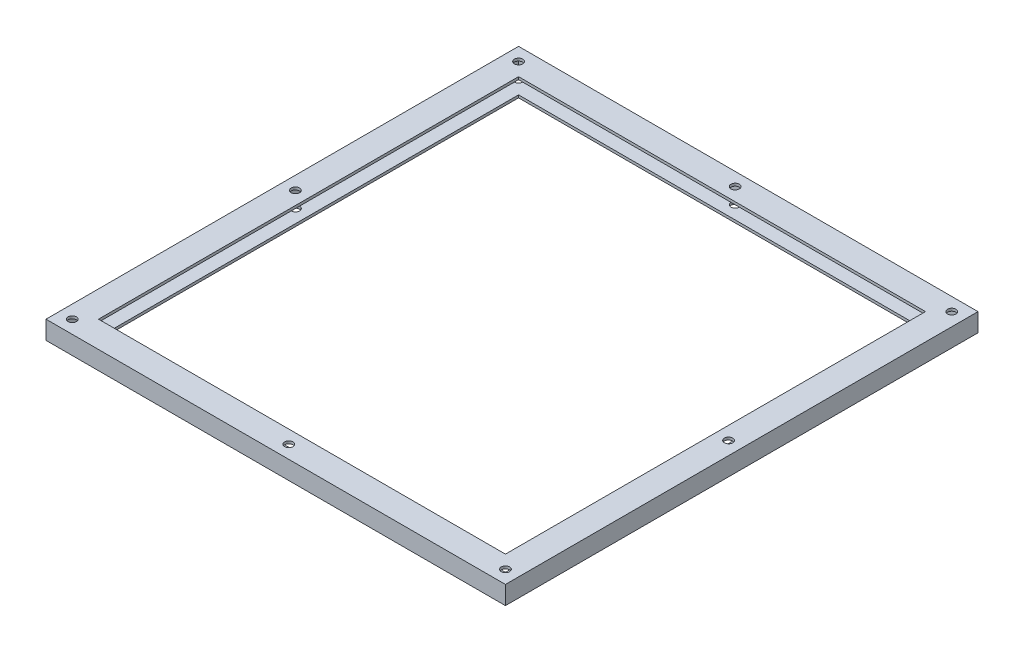
SolidWorks part; units mm, degrees
material "1.4000 (X6Cr13)"
ref_plane "Plan de face" through (0, 0, 0) normal (0, 0, 1) x (1, 0, 0)
ref_plane "Plan de dessus" through (0, 0, 0) normal (0, 1, 0) x (1, 0, 0)
ref_plane "Plan de droite" through (0, 0, 0) normal (1, 0, 0) x (0, 0, -1)
sketch "Esquisse1" plane through (0, 0, 0) normal (0, 1, 0) x (1, 0, 0)
  line L0 (0, 0) -> (350, 0)
  line L1 (350, 0) -> (350, 360)
  line L2 (350, 360) -> (0, 360)
  line L3 (0, 360) -> (0, 0)
  line L4 (20, 360) -> (20, 340) construction
  line L5 (20, 340) -> (330, 340)
  line L6 (330, 340) -> (330, 20)
  line L7 (330, 20) -> (20, 20)
  line L8 (20, 20) -> (20, 340)
  line L9 (40, 340) -> (40, 320) construction
  line L10 (40, 320) -> (310, 320) construction
  line L11 (310, 320) -> (310, 40) construction
  line L12 (310, 40) -> (40, 40) construction
  line L13 (40, 40) -> (40, 320) construction
  line L14 (0, 360) -> (40, 320) construction
  line L15 (350, 360) -> (310, 320) construction
  line L16 (310, 40) -> (350, 0) construction
  line L17 (40, 40) -> (0, 0) construction
  line L18 (310, 260) -> (250, 260) construction
  line L19 (250, 260) -> (250, 320) construction
  line L20 (2, 358) -> (348, 358)
  line L21 (348, 358) -> (348, 2)
  line L22 (348, 2) -> (2, 2)
  line L23 (2, 2) -> (2, 358)
  line L24 (340, 350) -> (10, 350) construction
  line L25 (10, 10) -> (340, 10) construction
  line L26 (340, 350) -> (340, 10) construction
  line L27 (10, 350) -> (10, 10) construction
  line L28 (20, 350) -> (10, 350) construction
  circle A0 centre (10, 10) radius 3.175
  circle A1 centre (175, 10) radius 3.175
  circle A2 centre (340, 10) radius 3.175
  circle A3 centre (340, 180) radius 3.175
  circle A4 centre (10, 180) radius 3.175
  circle A5 centre (340, 350) radius 3.175
  circle A6 centre (175, 350) radius 3.175
  circle A7 centre (10, 350) radius 3.175
  dimension "D16" = 280
  dimension "D1" = 20
  dimension "D2" = 20
  dimension "D3" = 20
  dimension "D4" = 350
  dimension "D5" = 360
  dimension "D6" = 20
  dimension "D7" = 310
  dimension "D8" = 320
  dimension "D9" = 20
  dimension "D10" = 20
  dimension "D11" = 20
  dimension "D12" = 20
  dimension "D13" = 60
  dimension "D14" = 60
  dimension "D15" = 270
  dimension "D17" = 2
extrude "Boss.-Extru.2" add sketch "Esquisse1" along normal blind 14 contours L23 L22 L21 L20 L7 L8 L5 L6 | L2 L3 L0 L1 L22 L23 L20 L21 region at (0.5021, 0, -180) region at (175, 0, -357.5036)
extrude "Enlèv. mat.-Extru.1" cut sketch "Esquisse1<4>" along normal blind 10 from offset 2 contours L23 L20 L21 L22
sketch "Esquisse1<4>" plane through (0, 0, 0) normal (0, 1, 0) x (1, 0, 0) same geometry as "Esquisse1"
